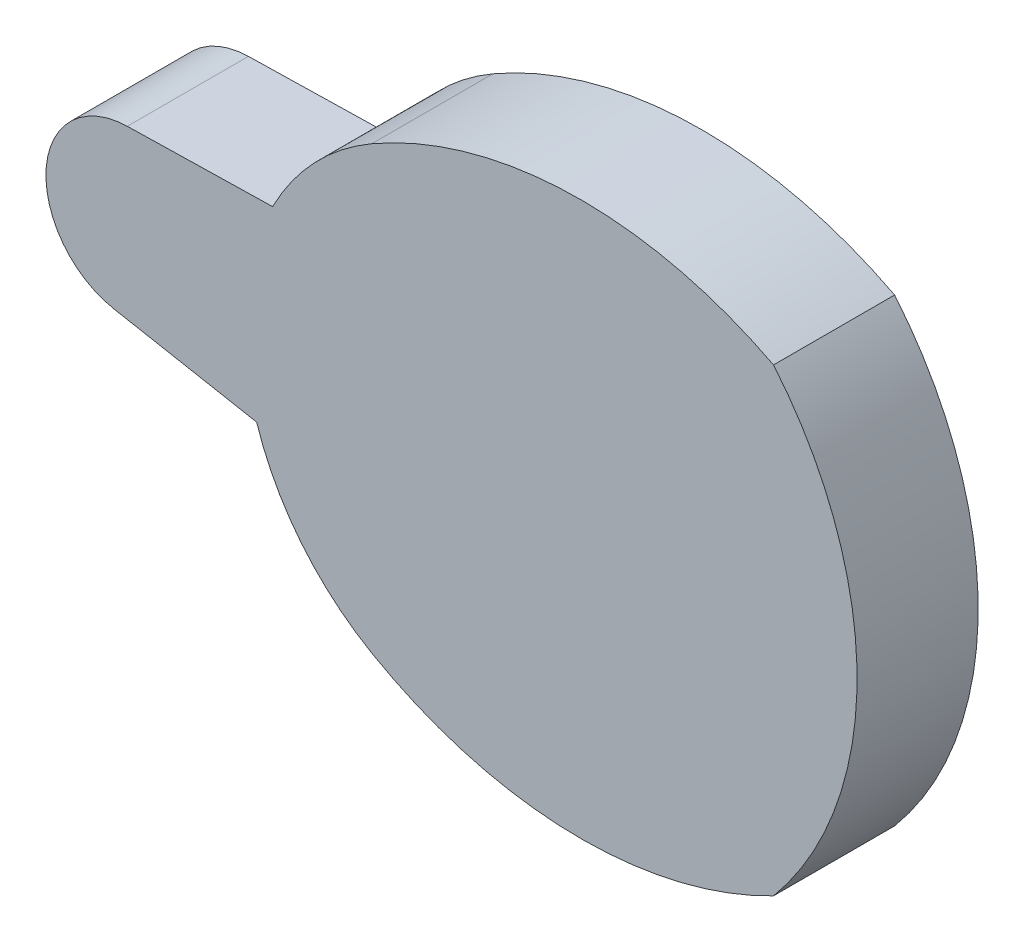
SolidWorks part; units mm, degrees
ref_plane "Front Plane" through (0, 0, 0) normal (0, 0, 1) x (1, 0, 0)
ref_plane "Top Plane" through (0, 0, 0) normal (0, 1, 0) x (1, 0, 0)
ref_plane "Right Plane" through (0, 0, 0) normal (1, 0, 0) x (0, 0, -1)
sketch "hose outline" plane through (0, 0, 0) normal (0, 0, 1) x (1, 0, 0)
  line L1 (-3.2131, 63.5) -> (3.2131, 63.5)
  line L2 (-3.2131, 63.5) -> (-3.2131, -63.5)
  line L3 (-3.2131, -63.5) -> (3.2131, -63.5)
  line L4 (3.2131, 63.5) -> (3.2131, -63.5)
  point P4 (0, 63.5)
  point P6 (-3.2131, 0)
  dimension "D1" = 6.4262
  dimension "D2" = 127
sketch "servo horn profile" plane through (0, 0, 0) normal (0, 0, 1) x (1, 0, 0)
  line L0 (-15.7102, 0) -> (-33.4308, 1.4527) construction
  line L1 (-15.7911, 3.8091) -> (-33.4728, 3.4335)
  line L2 (-33.7949, -0.4948) -> (-16.4104, -3.7451)
  line L3 (0, 0) -> (-15.7102, 0) construction
  circle A0 centre (-15.7102, 0) radius 3.81
  circle A1 centre (-33.4308, 1.4527) radius 1.9812
  dimension "D1" = 7.62
  dimension "D3" = 3.9624
  dimension "D2" = 17.78
  dimension "D4" = 15.7102
sketch "Cam diameters" plane through (0, 0, 0) normal (0, 0, 1) x (1, 0, 0)
  line L0 (3.2131, 63.5) -> (3.2131, -63.5) construction
  line L1 (-3.2131, 63.5) -> (-3.2131, -63.5) construction
  circle A0 centre (-15.7102, 0) radius 17.1453
  circle A1 centre (-15.7102, 0) radius 12.1971
  point P3 (3.2131, 0)
  point P7 (-3.5131, 0)
  point P8 (1.4351, 0)
  point P9 (-3.2131, 0)
  dimension "D1" = 1.778
  dimension "D2" = 0.3
sketch "Cam profile" plane through (0, 0, 0) normal (0, 0, 1) x (1, 0, 0)
  line L0 (-15.7102, 0) -> (-21.8088, 10.563) construction
  line L1 (0, 0) -> (-15.7102, 0) construction
  line L2 (0, 0) -> (-15.7102, 0) construction
  line L3 (-15.7102, 0) -> (-2.5672, 11.0102) construction
  line L4 (-34.1624, -2.4607) -> (-16.778, -5.711)
  line L5 (-33.5153, 5.433) -> (-15.8336, 5.8087)
  circle A0 centre (-15.7102, 0) radius 17.1453 construction
  circle A1 centre (-15.7102, 0) radius 12.1971 construction
  arc A2 (-2.5672, -11.0102) -> (-2.5672, 11.0102) centre (-15.7102, 0) ccw
  arc A3 (-21.8088, 10.563) -> (-21.8088, -10.563) centre (-15.7102, 0) ccw
  arc A4 (-21.8088, 10.563) -> (-2.5672, 11.0102) centre (-11.7791, -6.8089) cw
  arc A5 (-21.8088, -10.563) -> (-2.5672, -11.0102) centre (-11.7791, 6.8089) ccw
  circle A6 centre (-15.7102, 0) radius 5.81
  circle A7 centre (-33.4308, 1.4527) radius 3.9812
  circle A8 centre (-15.7102, 0) radius 3.81 construction
  circle A9 centre (-15.7102, 0) radius 3.81
  circle A10 centre (-33.4308, 1.4527) radius 1.9812 construction
  circle A11 centre (-33.4308, 1.4527) radius 1.9812
  point P18 (-15.7102, -5.81)
  point P21 (-15.7102, -3.81)
  point P22 (-37.412, 1.4527)
  point P25 (-35.412, 1.4527)
  dimension "D3" = 2
  dimension "D1" = 120
  dimension "D2" = 39.954
  dimension "D4" = 2
sketch "Servo Outline" plane through (0, 0, 0) normal (0, 0, 1) x (1, 0, 0)
  line L0 (-15.7102, 0) -> (-15.7102, 10.9) construction
  line L1 (-15.7102, 0) -> (-15.7102, -21.2) construction
  line L3 (-21.7102, 10.9) -> (-9.7102, 10.9)
  line L4 (-21.7102, 10.9) -> (-21.7102, -21.2)
  line L5 (-21.7102, -21.2) -> (-9.7102, -21.2)
  line L6 (-9.7102, 10.9) -> (-9.7102, -21.2)
  circle A0 centre (-15.7102, 0) radius 6
  point P9 (-15.7102, 10.9)
  point P10 (-15.7102, -21.2)
  dimension "D1" = 10.9
  dimension "D2" = 21.2
  dimension "D3" = 12
sketch "bearing" plane through (0, 0, 0) normal (0, 0, 1) x (1, 0, 0)
  line L0 (-2.5672, -11.0102) -> (-3.661, -9.6493) construction
  line L1 (-3.2843, -11.3629) -> (-2.0685, -10.3858) construction
  line L2 (-3.2843, -11.3629) -> (-2.5672, -11.0102) construction
  line L3 (-2.5672, -11.0102) -> (-2.0685, -10.3858) construction
  line L4 (-2.5672, -11.0102) -> (-2.4081, -11.2082) construction
  arc A0 (-21.8088, -10.563) -> (-2.5672, -11.0102) centre (-11.7791, 6.8089) ccw construction
  arc A1 (-2.5672, -11.0102) -> (-2.5672, 11.0102) centre (-15.7102, 0) ccw construction
  circle A2 centre (-3.661, -9.6493) radius 2
  point P11 (-2.6764, -10.8744)
  point P15 (-2.4081, -11.2082)
  dimension "D2" = 4
  dimension "D1" = 1.5597
  dimension "D3" = 0.254
sketch "Sketch7" plane through (0, 0, 0) normal (0, 0, 1) x (1, 0, 0)
  line L0 (-15.7911, 3.8091) -> (-33.4728, 3.4335) construction
  line L1 (-33.7949, -0.4948) -> (-16.4104, -3.7451) construction
  line L2 (-34.1624, -2.4607) -> (-16.778, -5.711) construction
  line L3 (-33.5153, 5.433) -> (-15.8336, 5.8087) construction
  line L4 (-15.7911, 3.8091) -> (-33.4728, 3.4335)
  line L5 (-33.7949, -0.4948) -> (-16.4104, -3.7451)
  line L6 (-34.1624, -2.4607) -> (-27.3197, -3.7401)
  line L7 (-33.5153, 5.433) -> (-26.5556, 5.5809)
  circle A0 centre (-33.4308, 1.4527) radius 1.9812 construction
  circle A1 centre (-15.7102, 0) radius 3.81 construction
  arc A3 (-2.5672, 11.0102) -> (-21.8088, 10.563) centre (-11.7791, -6.8089) ccw construction
  arc A4 (-21.8088, -10.563) -> (-2.5672, -11.0102) centre (-11.7791, 6.8089) ccw construction
  arc A5 (-2.5672, -11.0102) -> (-2.5672, 11.0102) centre (-15.7102, 0) ccw construction
  arc A6 (-21.8088, 10.563) -> (-21.8088, -10.563) centre (-15.7102, 0) ccw construction
  circle A7 centre (-33.4308, 1.4527) radius 1.9812
  arc A8 (-16.4104, -3.7451) -> (-15.7911, 3.8091) centre (-15.7102, 0) ccw
  arc A10 (-2.5672, 11.0102) -> (-21.8088, 10.563) centre (-11.7791, -6.8089) ccw
  arc A11 (-21.8088, -10.563) -> (-2.5672, -11.0102) centre (-11.7791, 6.8089) ccw
  arc A12 (-2.5672, -11.0102) -> (-2.5672, 11.0102) centre (-15.7102, 0) ccw
  arc A13 (-21.8088, 10.563) -> (-26.5556, 5.5809) centre (-15.7102, 0) ccw
  arc A14 (-27.3197, -3.7401) -> (-21.8088, -10.563) centre (-15.7102, 0) ccw
  arc A15 (-27.3753, 3.563) -> (-27.7998, -1.6156) centre (-15.7102, 0) ccw
  arc A16 (-33.5153, 5.433) -> (-34.1624, -2.4607) centre (-33.4308, 1.4527) ccw
extrude "Boss-Extrude1" add sketch "Sketch7" along normal blind 3.8 contours L7 A16 L6 A14 A11 A12 A10 A13 A8 L5 A7 L4 region at (-36.93, 1.7396, 0)
sketch "Sketch8" plane through (0, 0, 3.8) normal (0, 0, 1) x (1, 0, 0)
  line L2 (-26.5556, 5.5809) -> (-33.5153, 5.433)
  line L3 (-34.1624, -2.4607) -> (-27.3197, -3.7401)
  line L4 (-26.5556, 5.5809) -> (-33.5153, 5.433)
  line L5 (-34.1624, -2.4607) -> (-27.3197, -3.7401)
  arc A6 (-33.5153, 5.433) -> (-34.1624, -2.4607) centre (-33.4308, 1.4527) ccw
  arc A7 (-27.3197, -3.7401) -> (-21.8088, -10.563) centre (-15.7102, 0) ccw
  arc A8 (-21.8088, -10.563) -> (-2.5672, -11.0102) centre (-11.7791, 6.8089) ccw
  arc A9 (-2.5672, -11.0102) -> (-2.5672, 11.0102) centre (-15.7102, 0) ccw
  arc A10 (-2.5672, 11.0102) -> (-21.8088, 10.563) centre (-11.7791, -6.8089) ccw
  arc A11 (-21.8088, 10.563) -> (-26.5556, 5.5809) centre (-15.7102, 0) ccw
  arc A12 (-33.5153, 5.433) -> (-34.1624, -2.4607) centre (-33.4308, 1.4527) ccw
  arc A13 (-27.3197, -3.7401) -> (-21.8088, -10.563) centre (-15.7102, 0) ccw
  arc A14 (-21.8088, -10.563) -> (-2.5672, -11.0102) centre (-11.7791, 6.8089) ccw
  arc A15 (-2.5672, -11.0102) -> (-2.5672, 11.0102) centre (-15.7102, 0) ccw
  arc A16 (-2.5672, 11.0102) -> (-21.8088, 10.563) centre (-11.7791, -6.8089) ccw
  arc A17 (-21.8088, 10.563) -> (-26.5556, 5.5809) centre (-15.7102, 0) ccw
  dimension "D1" = 0
extrude "Boss-Extrude2" add sketch "Sketch8" along normal blind 2
